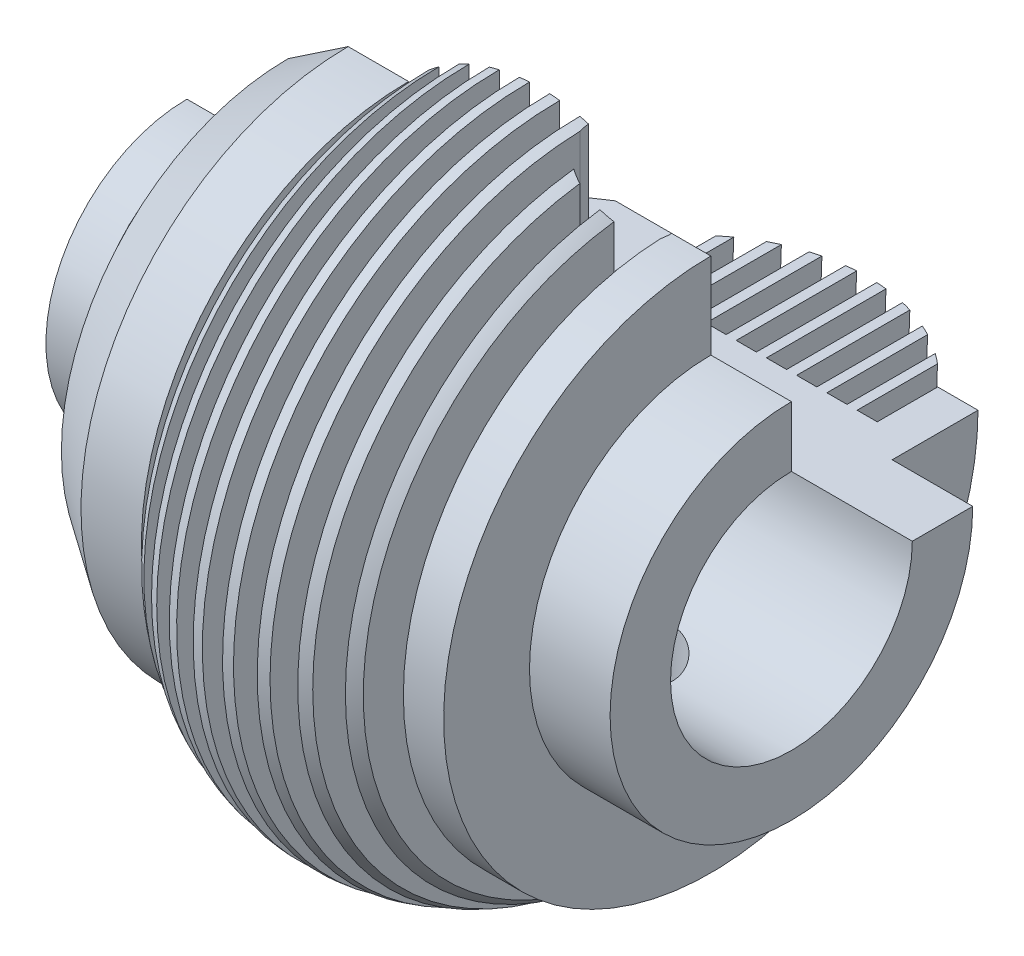
SolidWorks part; units mm, degrees
ref_plane "Alzado" through (0, 0, 0) normal (0, 0, 1) x (1, 0, 0)
ref_plane "Planta" through (0, 0, 0) normal (0, 1, 0) x (1, 0, 0)
ref_plane "Vista lateral" through (0, 0, 0) normal (1, 0, 0) x (0, 0, -1)
sketch "Croquis1" plane through (0, 0, 0) normal (0, 0, 1) x (1, 0, 0)
  line L0 (-75, -15) -> (75, -15) construction
  line L1 (-25, 0) -> (-75, 0)
  line L2 (-75, 0) -> (-75, 20)
  line L3 (-25, 0) -> (-25, 15)
  line L4 (-25, 15) -> (75, 15)
  line L5 (75, 15) -> (75, 30)
  line L6 (75, 30) -> (55, 30)
  line L7 (55, 30) -> (55, 51.3)
  line L8 (55, 51.3) -> (45, 51.3)
  line L9 (45, 51.3) -> (45, 36.3)
  line L10 (45, 36.3) -> (40, 36.3)
  line L11 (-20, 36.3) -> (-20, 51.3)
  line L12 (-20, 51.3) -> (-35, 51.3)
  line L13 (-35, 51.3) -> (-49.9227, 41.2345)
  line L14 (-49.9227, 41.2345) -> (-49.9227, 19.9345)
  line L15 (-75, 20) -> (-65, 20)
  line L16 (-65, 20) -> (-65, 10)
  line L17 (-65, 10) -> (-59.9227, 10)
  line L18 (-15, 36.3) -> (-15, 56.2468)
  line L19 (5, 36.3) -> (5, 15)
  line L20 (-12.5, 36.3) -> (-12.5, 58.1902)
  line L21 (-7.5, 36.3) -> (-7.5, 61.2902)
  line L22 (-5, 36.3) -> (-5, 62.5094)
  line L23 (0, 36.3) -> (0, 64.3846)
  line L24 (2.5, 36.3) -> (2.5, 65.066)
  line L25 (10, 36.3) -> (10, 66.1775)
  line L26 (7.5, 36.3) -> (7.5, 65.9575)
  line L27 (17.5, 36.3) -> (17.5, 65.9575)
  line L28 (15, 36.3) -> (15, 66.1775)
  line L29 (25, 36.3) -> (25, 64.3846)
  line L30 (22.5, 36.3) -> (22.5, 65.066)
  line L31 (32.5, 36.3) -> (32.5, 61.2902)
  line L32 (30, 36.3) -> (30, 62.5094)
  line L33 (40, 36.3) -> (40, 56.2468)
  line L34 (37.5, 36.3) -> (37.5, 58.1902)
  line L35 (-15, 36.3) -> (-15, 68.3076) construction
  line L36 (-12.5, 36.3) -> (-12.5, 69.1211) construction
  line L37 (-7.5, 36.3) -> (-7.5, 68.3076) construction
  line L38 (-5, 36.3) -> (-5, 69.1211) construction
  line L39 (0, 36.3) -> (0, 68.3076) construction
  line L40 (2.5, 36.3) -> (2.5, 69.1211) construction
  line L41 (10, 36.3) -> (10, 69.1211) construction
  line L42 (22.5, 36.3) -> (22.5, 68.3076) construction
  line L43 (25, 36.3) -> (25, 69.1211) construction
  line L44 (30, 36.3) -> (30, 68.3076) construction
  line L45 (32.5, 36.3) -> (32.5, 69.1211) construction
  line L46 (37.5, 36.3) -> (37.5, 68.3076) construction
  line L47 (40, 36.3) -> (40, 69.1211) construction
  line L48 (17.5, 36.3) -> (17.5, 69.1211) construction
  line L49 (15, 36.3) -> (15, 68.3076) construction
  line L50 (7.5, 36.3) -> (7.5, 68.3076) construction
  line L51 (-7.5, 36.3) -> (-12.5, 36.3)
  line L52 (-15, 36.3) -> (-20, 36.3)
  line L53 (0, 36.3) -> (-5, 36.3)
  line L54 (7.5, 36.3) -> (2.5, 36.3)
  line L55 (15, 36.3) -> (10, 36.3)
  line L56 (22.5, 36.3) -> (17.5, 36.3)
  line L57 (30, 36.3) -> (25, 36.3)
  line L58 (37.5, 36.3) -> (32.5, 36.3)
  line L59 (20, 36.3) -> (20, 15)
  arc A1 (-59.9227, 10) -> (-49.9227, 20) centre (-59.9227, 20) ccw
  arc A2 (-15, 56.2468) -> (-12.5, 58.1902) centre (12.5, 23.4506) cw
  arc A3 (0, 64.3846) -> (2.5, 65.066) centre (12.5, 23.4506) cw
  arc A4 (7.5, 65.9575) -> (10, 66.1775) centre (12.5, 23.4506) cw
  arc A5 (15, 66.1775) -> (17.5, 65.9575) centre (12.5, 23.4506) cw
  arc A6 (-7.5, 61.2902) -> (-5, 62.5094) centre (12.5, 23.4506) cw
  arc A7 (37.5, 58.1902) -> (40, 56.2468) centre (12.5, 23.4506) cw
  arc A8 (30, 62.5094) -> (32.5, 61.2902) centre (12.5, 23.4506) cw
  arc A9 (22.5, 65.066) -> (25, 64.3846) centre (12.5, 23.4506) cw
  point P2 (0, -15)
  dimension "D10" = 21.3
  dimension "D18" = 20
  dimension "D22" = 42.8
  dimension "D26" = 5
  dimension "D32" = 5
  dimension "D1" = 150
  dimension "D2" = 15
  dimension "D3" = 0
  dimension "D4" = 50
  dimension "D5" = 20
  dimension "D6" = 15
  dimension "D7" = 100
  dimension "D8" = 15
  dimension "D9" = 20
  dimension "D11" = 10
  dimension "D12" = 15
  dimension "D13" = 65
  dimension "D14" = 15
  dimension "D15" = 15
  dimension "D16" = 146
  dimension "D17" = 18
  dimension "D19" = 21.3
  dimension "D20" = 10
  dimension "D21" = 10
  dimension "D23" = 5
  dimension "D24" = 75
  dimension "D25" = 2.5
  dimension "D27" = 5
  dimension "D28" = 5
  dimension "D29" = 5
  dimension "D30" = 5
  dimension "D31" = 5
sketch "Croquis2" plane through (0, 0, 0) normal (0, 0, 1) x (1, 0, 0)
  line L0 (-25, 0) -> (-25, 15) construction
  line L1 (-65, 10) -> (-59.9227, 10) construction
  line L2 (-65, 20) -> (-65, 10) construction
  line L3 (-75, 20) -> (-65, 20) construction
  line L4 (-25, 0) -> (-75, 0) construction
  line L5 (-75, 0) -> (-75, 20) construction
  line L6 (-25, 0) -> (-25, 15)
  line L7 (-65, 10) -> (-59.9227, 10)
  line L8 (-65, 20) -> (-65, 10)
  line L9 (-75, 20) -> (-65, 20)
  line L10 (-25, 0) -> (-75, 0)
  line L11 (-75, 0) -> (-75, 20)
  line L14 (-25, 15) -> (75, 15) construction
  line L18 (-25, 15) -> (75, 15)
  line L19 (55, 30) -> (55, 51.3) construction
  line L20 (75, 30) -> (55, 30) construction
  line L21 (75, 15) -> (75, 30) construction
  line L22 (55, 30) -> (55, 51.3)
  line L23 (75, 30) -> (55, 30)
  line L24 (75, 15) -> (75, 30)
  line L25 (45, 36.3) -> (40, 36.3) construction
  line L26 (55, 51.3) -> (45, 51.3) construction
  line L27 (45, 36.3) -> (40, 36.3)
  line L28 (55, 51.3) -> (45, 51.3)
  line L29 (-20, 36.3) -> (-20, 51.3) construction
  line L30 (-15, 36.3) -> (-20, 36.3) construction
  line L31 (-15, 36.3) -> (-15, 56.2468) construction
  line L32 (-12.5, 36.3) -> (-12.5, 58.1902) construction
  line L33 (-7.5, 36.3) -> (-12.5, 36.3) construction
  line L34 (-7.5, 36.3) -> (-7.5, 61.2902) construction
  line L35 (0, 36.3) -> (-5, 36.3) construction
  line L36 (-5, 36.3) -> (-5, 62.5094) construction
  line L37 (0, 36.3) -> (0, 64.3846) construction
  line L38 (2.5, 36.3) -> (2.5, 65.066) construction
  line L39 (7.5, 36.3) -> (2.5, 36.3) construction
  line L40 (7.5, 36.3) -> (7.5, 65.9575) construction
  line L41 (10, 36.3) -> (10, 66.1775) construction
  line L42 (15, 36.3) -> (10, 36.3) construction
  line L43 (15, 36.3) -> (15, 66.1775) construction
  line L44 (17.5, 36.3) -> (17.5, 65.9575) construction
  line L45 (22.5, 36.3) -> (17.5, 36.3) construction
  line L46 (22.5, 36.3) -> (22.5, 65.066) construction
  line L47 (25, 36.3) -> (25, 64.3846) construction
  line L48 (30, 36.3) -> (25, 36.3) construction
  line L49 (30, 36.3) -> (30, 62.5094) construction
  line L50 (32.5, 36.3) -> (32.5, 61.2902) construction
  line L51 (37.5, 36.3) -> (32.5, 36.3) construction
  line L52 (37.5, 36.3) -> (37.5, 58.1902) construction
  line L53 (40, 36.3) -> (40, 56.2468) construction
  line L54 (45, 51.3) -> (45, 36.3) construction
  line L55 (-20, 36.3) -> (-20, 51.3)
  line L56 (-15, 36.3) -> (-20, 36.3)
  line L57 (-15, 36.3) -> (-15, 56.2468)
  line L58 (-12.5, 36.3) -> (-12.5, 58.1902)
  line L59 (-7.5, 36.3) -> (-12.5, 36.3)
  line L60 (-7.5, 36.3) -> (-7.5, 61.2902)
  line L61 (0, 36.3) -> (-5, 36.3)
  line L62 (-5, 36.3) -> (-5, 62.5094)
  line L63 (0, 36.3) -> (0, 64.3846)
  line L64 (2.5, 36.3) -> (2.5, 65.066)
  line L65 (7.5, 36.3) -> (2.5, 36.3)
  line L66 (7.5, 36.3) -> (7.5, 65.9575)
  line L67 (10, 36.3) -> (10, 66.1775)
  line L68 (15, 36.3) -> (10, 36.3)
  line L69 (15, 36.3) -> (15, 66.1775)
  line L70 (17.5, 36.3) -> (17.5, 65.9575)
  line L71 (22.5, 36.3) -> (17.5, 36.3)
  line L72 (22.5, 36.3) -> (22.5, 65.066)
  line L73 (25, 36.3) -> (25, 64.3846)
  line L74 (30, 36.3) -> (25, 36.3)
  line L75 (30, 36.3) -> (30, 62.5094)
  line L76 (32.5, 36.3) -> (32.5, 61.2902)
  line L77 (37.5, 36.3) -> (32.5, 36.3)
  line L78 (37.5, 36.3) -> (37.5, 58.1902)
  line L79 (40, 36.3) -> (40, 56.2468)
  line L80 (45, 51.3) -> (45, 36.3)
  line L81 (-20, 51.3) -> (-35, 51.3) construction
  line L82 (-20, 51.3) -> (-35, 51.3)
  line L83 (-35, 51.3) -> (-49.9227, 41.2345) construction
  line L84 (-35, 51.3) -> (-49.9227, 41.2345)
  line L85 (-49.9227, 41.2345) -> (-49.9227, 20)
  arc A0 (-59.9227, 10) -> (-49.9227, 20) centre (-59.9227, 20) ccw construction
  arc A1 (-59.9227, 10) -> (-49.9227, 20) centre (-59.9227, 20) ccw
  arc A2 (-12.5, 58.1902) -> (-15, 56.2468) centre (12.5, 23.4506) ccw construction
  arc A3 (-5, 62.5094) -> (-7.5, 61.2902) centre (12.5, 23.4506) ccw construction
  arc A4 (2.5, 65.066) -> (0, 64.3846) centre (12.5, 23.4506) ccw construction
  arc A5 (10, 66.1775) -> (7.5, 65.9575) centre (12.5, 23.4506) ccw construction
  arc A6 (17.5, 65.9575) -> (15, 66.1775) centre (12.5, 23.4506) ccw construction
  arc A7 (25, 64.3846) -> (22.5, 65.066) centre (12.5, 23.4506) ccw construction
  arc A8 (32.5, 61.2902) -> (30, 62.5094) centre (12.5, 23.4506) ccw construction
  arc A9 (40, 56.2468) -> (37.5, 58.1902) centre (12.5, 23.4506) ccw construction
  arc A10 (-12.5, 58.1902) -> (-15, 56.2468) centre (12.5, 23.4506) ccw
  arc A11 (-5, 62.5094) -> (-7.5, 61.2902) centre (12.5, 23.4506) ccw
  arc A12 (2.5, 65.066) -> (0, 64.3846) centre (12.5, 23.4506) ccw
  arc A13 (10, 66.1775) -> (7.5, 65.9575) centre (12.5, 23.4506) ccw
  arc A14 (17.5, 65.9575) -> (15, 66.1775) centre (12.5, 23.4506) ccw
  arc A15 (25, 64.3846) -> (22.5, 65.066) centre (12.5, 23.4506) ccw
  arc A16 (32.5, 61.2902) -> (30, 62.5094) centre (12.5, 23.4506) ccw
  arc A17 (40, 56.2468) -> (37.5, 58.1902) centre (12.5, 23.4506) ccw
revolve "Revolución2" add sketch "Croquis2" angle 270 about L0
sketch "Croquis12" plane through (0, 0, 0) normal (0, 1, 0) x (1, 0, 0)
  line L0 (-75, 0) -> (75, 0) construction
  line L1 (55, -45) -> (55, 45) construction
  circle A0 centre (35, 0) radius 10.308
  dimension "D1" = 20
extrude "Cortar-Extruir1" cut sketch "Croquis12" along normal through all
extrude "Cortar-Extruir2" cut sketch "Croquis12<2>" against normal through all
sketch "Croquis12<2>" plane through (0, 0, 0) normal (0, 1, 0) x (1, 0, 0) same geometry as "Croquis12"
